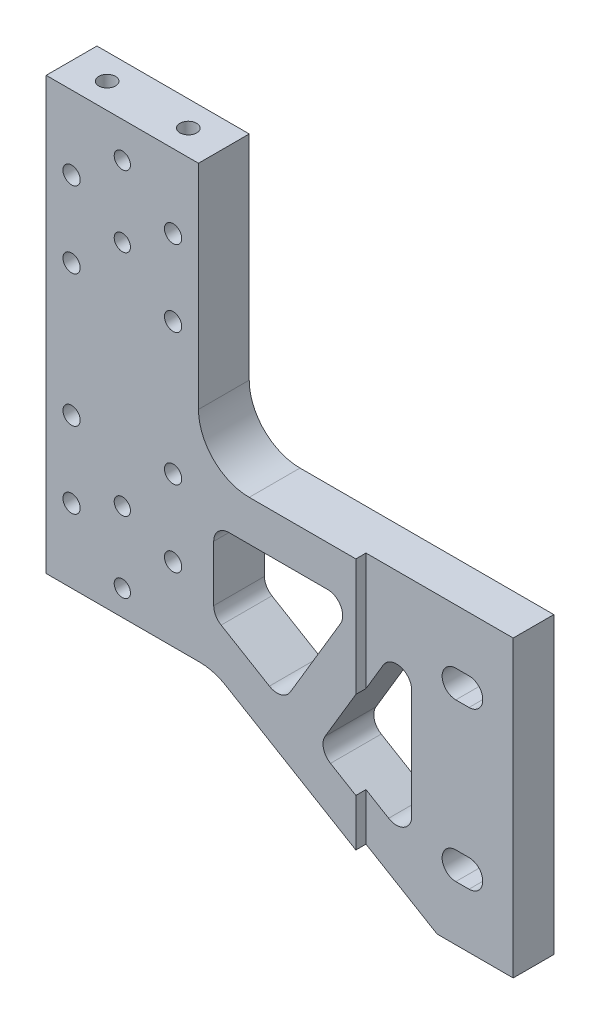
SolidWorks part; units mm, degrees
material "1060 Legierung"
ref_plane "Ebene vorne" through (0, 0, 0) normal (0, 0, 1) x (1, 0, 0)
ref_plane "Ebene oben" through (0, 0, 0) normal (0, 1, 0) x (1, 0, 0)
ref_plane "Ebene rechts" through (0, 0, 0) normal (1, 0, 0) x (0, 0, -1)
sketch "Skizze1" plane through (0, 0, 0) normal (0, 0, 1) x (1, 0, 0)
  line L0 (28.7885, -29) -> (-13.2115, -4)
  line L1 (43.7885, 29) -> (-16.2115, 29)
  line L2 (43.7885, 29) -> (43.7885, -29)
  line L3 (43.7885, -29) -> (28.7885, -29)
  line L4 (-46.2115, -4) -> (-46.2115, 81)
  line L5 (-16.2115, 29) -> (-16.2115, 81)
  line L6 (-16.2115, 81) -> (-46.2115, 81)
  line L8 (-13.2115, -4) -> (-46.2115, -4)
  point P0 (0, 0)
  point P11 (43.7885, 0)
  dimension "D1" = 85
  dimension "D2" = 58
  dimension "D3" = 25
  dimension "D4" = 15
  dimension "D5" = 33
  dimension "D6" = 90
  dimension "D8" = 60
extrude "Aufsatz-Linear austragen1" add sketch "Skizze1" along normal blind 10
hole_wizard "Ø5.4 (5.4) Durchmesser Langloch4" positions "Skizze2" profile "Skizze3" size "Ø5.4" standard "DIN" slot yes end condition through all
sketch "Skizze2" plane through (0, 0, 10) normal (0, 0, 1) x (1, 0, 0)
  line L0 (43.7885, -29) -> (43.7885, 29) construction
  line L2 (29.7885, 15.5) -> (37.7885, 15.5) construction
  point P0 (33.7885, 15.5)
  point P2 (33.7885, -15.5)
  dimension "D1" = 31
  dimension "D2" = 10
  dimension "D3" = 15.5
  dimension "D4" = 8
sketch "Skizze3" plane through (33.7885, 15.5, 10) normal (1, 0, 0) x (0, -1, 0)
  line L0 (0, 0) -> (0, 10)
  line L1 (0, 10) -> (2.7, 10)
  line L2 (2.7, 10) -> (2.7, 0)
  line L5 (2.7, 0) -> (0, 0)
  line L11 (0, -6.35) -> (0, 107.95) construction
  dimension "Bohrerdurchmesser" = 5.4
  dimension "Bohrungstiefe" = 10
sketch "Skizze5" plane through (0, 0, 0) normal (0, 0, -1) x (-1, 0, 0)
  line L0 (-23.7885, -16.7138) -> (-23.7885, 21)
  line L1 (13.2115, 21) -> (13.2115, 5.31)
  line L2 (13.2115, 5.31) -> (-0.3384, -2.7554)
  line L3 (-14.4786, 21) -> (13.2115, 21)
  line L4 (-0.3384, -2.7554) -> (-14.4786, 21)
  line L5 (-23.7885, 21) -> (-7.2128, -6.8473)
  line L9 (-43.7885, 29) -> (16.2115, 29) construction
  line L10 (-7.2128, -6.8473) -> (-23.7885, -16.7138)
  line L11 (13.2115, -4) -> (-28.7885, -29) construction
  line L12 (-43.7885, -29) -> (-43.7885, 29) construction
  dimension "D1" = 8
  dimension "D2" = 8
  dimension "D3" = 8
  dimension "D7" = 20
extrude "Schnitt-Linear austragen1" cut sketch "Skizze5" against normal through all
fillet "Verrundung1" radius 3 7 edges at (0.3384, -2.7554, 5) (-13.2115, 21, 5) (-13.2115, 5.31, 5) (7.2128, -6.8473, 5) (23.7885, -16.7138, 5) (14.4786, 21, 5) (23.7885, 21, 5)
hole_wizard "M4 Gewindebohrung2" positions "Skizze6" profile "Skizze7" tap size "M4" standard "DIN"
sketch "Skizze6" plane through (0, -4, 0) normal (0, -1, 0) x (-1, 0, 0)
  line L5 (46.2115, -10) -> (46.2115, 0) construction
  point P0 (23.2115, -5)
  point P2 (39.2115, -5)
  dimension "D1" = 16
  dimension "D2" = 5
  dimension "D3" = 7
cosmetic thread "Bohrungsgewinde1" parameters "D1"=8, "D2"=4
cosmetic thread "Bohrungsgewinde2" parameters "D1"=8, "D2"=4
sketch "Skizze7" plane through (-23.2115, -4, 5) normal (1, 0, 0) x (0, 0, -1)
  line L0 (0, 0) -> (0, 12.4914)
  line L1 (0, 12.4914) -> (1.65, 11.5)
  line L2 (1.65, 11.5) -> (1.65, 0)
  line L5 (1.65, 0) -> (0, 0)
  line L10 (0, 12.4914) -> (-1.65, 11.5) construction
  line L11 (0, -6.35) -> (0, 107.95) construction
  dimension "Bohrerdurchmesser" = 3.3
  dimension "Bohrungstiefe" = 11.5
  dimension "Spitzenwinkel" = 118
hole_wizard "Formsenkung für M3 Senkschraube mit Schlitz/Kreuzschlitz1" positions "Skizze8" profile "Skizze9" countersink size "M3" standard "DIN" end condition through all
sketch "Skizze8" plane through (0, 0, 0) normal (0, 0, 1) x (1, 0, 0)
  line L1 (-46.2115, -4) -> (-13.2115, -4) construction
  line L2 (-31.2115, 81) -> (-31.2115, -4) construction
  line L3 (-16.2115, 81) -> (-46.2115, 81) construction
  point P0 (-31.2115, 15)
  point P2 (-31.2115, 1)
  point P19 (-31.2115, 74)
  point P21 (-31.2115, 60)
  dimension "D1" = 14
  dimension "D2" = 14
  dimension "D3" = 5
  dimension "D4" = 45
sketch "Skizze9" plane through (-31.2115, 15, 0) normal (1, 0, 0) x (0, 1, 0)
  line L0 (0, 0) -> (0, 10)
  line L1 (0, 10) -> (1.6, 10)
  line L2 (1.6, 10) -> (1.6, 1.55)
  line L3 (1.6, 1.55) -> (3.15, 0)
  line L5 (3.15, 0) -> (0, 0)
  line L6 (-1.6, 1.55) -> (-3.15, 0) construction
  line L11 (0, -6.35) -> (0, 107.95) construction
  dimension "Bohrerdurchmesser" = 3.2
  dimension "Bohrungstiefe" = 10
  dimension "Senkdurchmesser (Oben)" = 6.3
  dimension "Senkwinkel (Oben)" = 90
hole_wizard "M4 Gewindebohrung1" positions "Skizze10" profile "Skizze11" tap size "M4" standard "DIN"
sketch "Skizze10" plane through (0, 81, 0) normal (0, 1, 0) x (1, 0, 0)
  line L0 (-46.2115, -5) -> (-16.2115, -5) construction
  line L1 (-46.2115, -10) -> (-46.2115, 0) construction
  line L2 (-16.2115, -10) -> (-16.2115, 0) construction
  point P0 (-39.2115, -5)
  point P2 (-23.2115, -5)
  dimension "D1" = 16
  dimension "D2" = 7
sketch "Skizze11" plane through (-39.2115, 81, 5) normal (1, 0, 0) x (0, 0, 1)
  line L0 (0, 0) -> (0, 12.4914)
  line L1 (0, 12.4914) -> (1.65, 11.5)
  line L2 (1.65, 11.5) -> (1.65, 0)
  line L5 (1.65, 0) -> (0, 0)
  line L10 (0, 12.4914) -> (-1.65, 11.5) construction
  line L11 (0, -6.35) -> (0, 107.95) construction
  dimension "Bohrerdurchmesser" = 3.3
  dimension "Bohrungstiefe" = 11.5
  dimension "Spitzenwinkel" = 118
cosmetic thread "Bohrungsgewinde5" parameters "D1"=8, "D2"=4
cosmetic thread "Bohrungsgewinde6" parameters "D1"=8, "D2"=4
fillet "Verrundung2" radius 10 2 edges at (-13.2115, -4, 5) (-16.2115, 29, 5)
sketch "Skizze13" plane through (0, 0, 10) normal (0, 0, 1) x (1, 0, 0)
  line L0 (43.7885, -29) -> (43.7885, 29)
  line L1 (43.7885, 29) -> (14.7885, 29)
  line L2 (43.7885, 29) -> (-6.2115, 29) construction
  line L3 (14.7885, 29) -> (14.7885, -29)
  line L4 (14.7885, -29) -> (43.7885, -29)
  dimension "D1" = 29
extrude "Schnitt-Linear austragen2" cut sketch "Skizze13" against normal blind 2
hole_wizard "Formsenkung für M3 Linsensenkschraube mit Schlitz1" positions "Skizze14" profile "Skizze15" countersink size "M3" standard "DIN" end condition through all
sketch "Skizze14" plane through (0, 0, 0) normal (0, 0, -1) x (-1, 0, 0)
  line L4 (31.2115, 81) -> (31.2115, -4) construction
  line L5 (16.2115, 81) -> (46.2115, 81) construction
  point P0 (21.2115, 66.5)
  point P2 (21.2115, 51.5)
  point P4 (41.2115, 66.5)
  point P6 (41.2115, 51.5)
  point P8 (21.2115, 25.5)
  point P10 (21.2115, 10.5)
  point P12 (41.2115, 25.5)
  point P14 (41.2115, 10.5)
  dimension "D1" = 15
  dimension "D2" = 20
  dimension "D3" = 15
  dimension "D4" = 14.5
  dimension "D5" = 55.5
sketch "Skizze15" plane through (-21.2115, 66.5, 0) normal (1, 0, 0) x (0, 1, 0)
  line L0 (0, 0) -> (0, 10)
  line L1 (0, 10) -> (1.7, 10)
  line L2 (1.7, 10) -> (1.7, 1.45)
  line L3 (1.7, 1.45) -> (3.15, 0)
  line L5 (3.15, 0) -> (0, 0)
  line L6 (-1.7, 1.45) -> (-3.15, 0) construction
  line L11 (0, -6.35) -> (0, 107.95) construction
  dimension "Bohrerdurchmesser" = 3.4
  dimension "Bohrungstiefe" = 10
  dimension "Senkdurchmesser (Oben)" = 6.3
  dimension "Senkwinkel (Oben)" = 90
hole_wizard "M4 Gewindebohrung3" positions "Skizze16" profile "Skizze17" tap size "M4" standard "DIN"
sketch "Skizze16" plane through (-46.2115, 0, 0) normal (-1, 0, 0) x (0, 0, 1)
  line L0 (5, 81) -> (5, -4) construction
  line L1 (10, 81) -> (0, 81) construction
  line L2 (10, -4) -> (0, -4) construction
  point P0 (5, 39)
  point P2 (5, 18)
  point P18 (5, 60)
  dimension "D1" = 21
  dimension "D2" = 21
  dimension "D3" = 21
cosmetic thread "Bohrungsgewinde15" parameters "D1"=8, "D2"=4
cosmetic thread "Bohrungsgewinde16" parameters "D1"=8, "D2"=4
sketch "Skizze17" plane through (-46.2115, 39, 5) normal (0, 1, 0) x (0, 0, 1)
  line L0 (0, 0) -> (0, 12.4914)
  line L1 (0, 12.4914) -> (1.65, 11.5)
  line L2 (1.65, 11.5) -> (1.65, 0.375)
  line L3 (1.65, 0.375) -> (2.025, 0)
  line L5 (2.025, 0) -> (0, 0)
  line L6 (-1.65, 0.375) -> (-2.025, 0) construction
  line L10 (0, 12.4914) -> (-1.65, 11.5) construction
  line L11 (0, -6.35) -> (0, 107.95) construction
  dimension "Bohrerdurchmesser" = 3.3
  dimension "Bohrungstiefe" = 11.5
  dimension "Senkdurchmesser (Oben)" = 4.05
  dimension "Senkwinkel (Oben)" = 90
  dimension "Spitzenwinkel" = 118
cosmetic thread "Bohrungsgewinde17" parameters "D1"=8, "D2"=4
